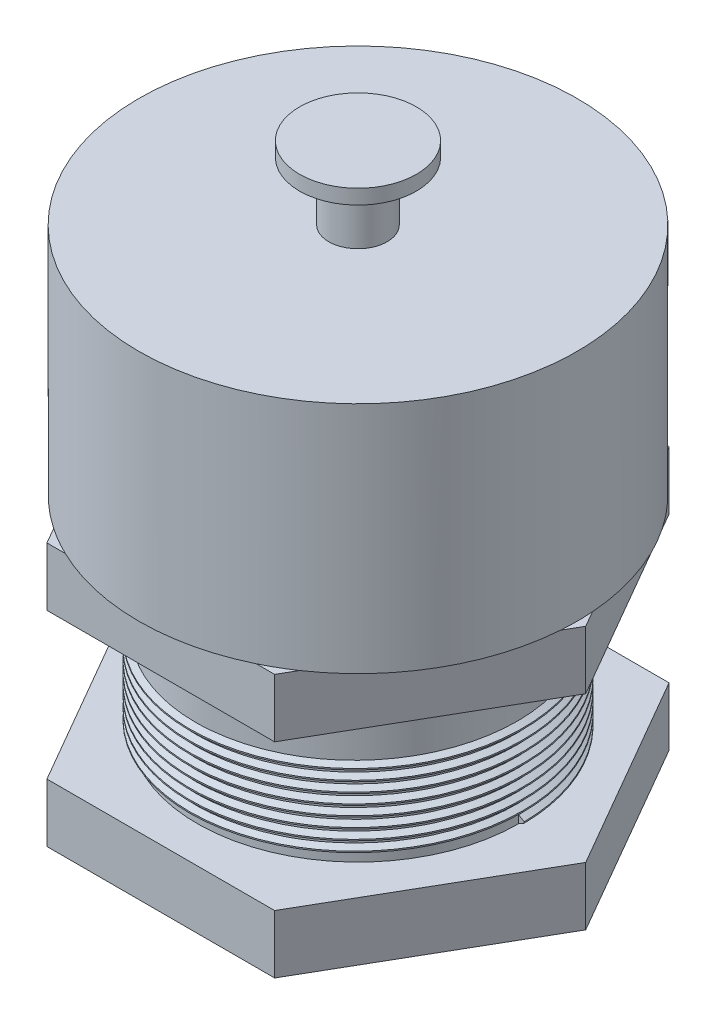
SolidWorks part; units mm, degrees
ref_plane "前视基准面" through (0, 0, 0) normal (0, 0, 1) x (1, 0, 0)
ref_plane "上视基准面" through (0, 0, 0) normal (0, 1, 0) x (1, 0, 0)
ref_plane "右视基准面" through (0, 0, 0) normal (1, 0, 0) x (0, 0, -1)
sketch "草图1" plane through (0, 0, 0) normal (0, 1, 0) x (1, 0, 0)
  line L1 (3.8971, -6.75) -> (7.7942, 0)
  line L2 (7.7942, 0) -> (3.8971, 6.75)
  line L3 (3.8971, 6.75) -> (-3.8971, 6.75)
  line L4 (-3.8971, 6.75) -> (-7.7942, 0)
  line L5 (-7.7942, 0) -> (-3.8971, -6.75)
  line L6 (-3.8971, -6.75) -> (3.8971, -6.75)
  circle A0 centre (0, 0) radius 6.75 construction
  dimension "D1" = 13.5
extrude "凸台-拉伸1" add sketch "草图1" along normal blind 2
sketch "草图2" plane through (0, 2, 0) normal (0, 1, 0) x (1, 0, 0)
  circle A0 centre (0, 0) radius 5.5
  dimension "D1" = 11
extrude "凸台-拉伸2" add sketch "草图2" along normal blind 5
thread "螺纹线1" pitch 0.35 method extrude profile "螺纹线轮廓1" start angle 0, offset 0, length 3, pitch 0.35, diameter 11
ref_plane "基准面1" through (5.5, 2, 0) normal (0, 0, 1) x (1, 0, 0)
sketch "螺纹线轮廓1" plane through (5.5, 2, 0) normal (0, 0, 1) x (1, 0, 0)
  line L0 (0, 0) -> (0, 0.35) construction
  line L1 (0, 0) -> (0.1894, 0.1094)
  line L2 (0.1894, 0.1094) -> (0.1894, 0.1531)
  line L3 (0.1894, 0.1531) -> (0, 0.2625)
  line L4 (0.1894, 0.1312) -> (0, 0.1312) construction
  line L11 (0, 0) -> (0, 0.2625)
  point P2 (0, 0)
  dimension "Pitch" = 0.35
  dimension "Profile_Angle" = 60
  dimension "Profile_Land" = 0.0437
  dimension "Profile_Height" = 0.1894
sketch "草图6" plane through (0, 7, 0) normal (0, 1, 0) x (1, 0, 0)
  line L1 (3.8971, -6.75) -> (7.7942, 0)
  line L2 (7.7942, 0) -> (3.8971, 6.75)
  line L3 (3.8971, 6.75) -> (-3.8971, 6.75)
  line L4 (-3.8971, 6.75) -> (-7.7942, 0)
  line L5 (-7.7942, 0) -> (-3.8971, -6.75)
  line L6 (-3.8971, -6.75) -> (3.8971, -6.75)
  circle A0 centre (0, 0) radius 6.75 construction
  dimension "D1" = 13.5
extrude "凸台-拉伸3" add sketch "草图6" along normal blind 2
sketch "草图7" plane through (0, 9, 0) normal (0, 1, 0) x (1, 0, 0)
  circle A0 centre (0, 0) radius 7.5
  dimension "D1" = 15
extrude "凸台-拉伸4" add sketch "草图7" along normal blind 8
sketch "草图8" plane through (0, 17, 0) normal (0, 1, 0) x (1, 0, 0)
  circle A0 centre (0, 0) radius 1
  dimension "D1" = 2
extrude "凸台-拉伸5" add sketch "草图8" along normal blind 2
sketch "草图9" plane through (0, 19, 0) normal (0, 1, 0) x (1, 0, 0)
  circle A0 centre (0, 0) radius 2
  dimension "D1" = 4
extrude "凸台-拉伸6" add sketch "草图9" along normal blind 0.5
